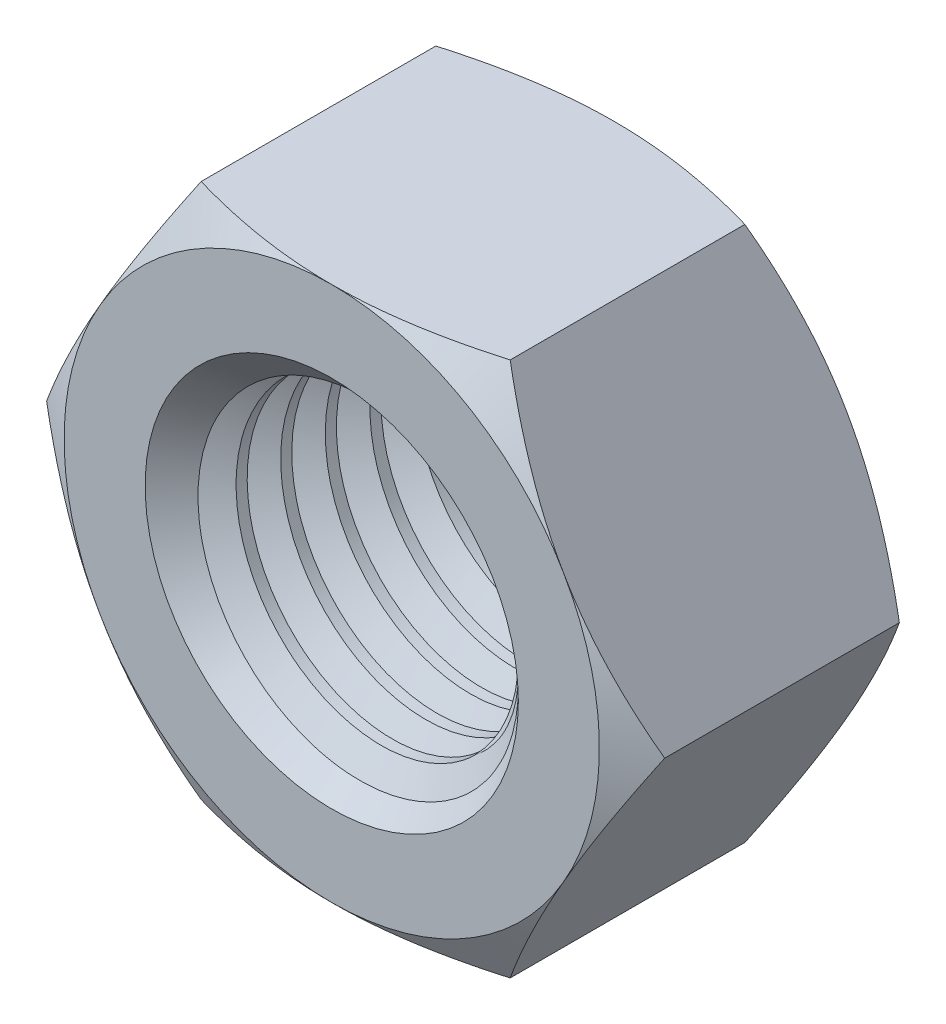
SolidWorks part; units mm, degrees
ref_plane "Front" through (0, 0, 0) normal (0, 0, 1) x (1, 0, 0)
ref_plane "Top" through (0, 0, 0) normal (0, 1, 0) x (1, 0, 0)
ref_plane "Right" through (0, 0, 0) normal (1, 0, 0) x (0, 0, -1)
sketch "Çizim1" plane through (0, 0, 0) normal (0, 0, 1) x (1, 0, 0)
  line L1 (20.7846, 0) -> (10.3923, 18)
  line L2 (10.3923, 18) -> (-10.3923, 18)
  line L3 (-10.3923, 18) -> (-20.7846, 0)
  line L4 (-20.7846, 0) -> (-10.3923, -18)
  line L5 (-10.3923, -18) -> (10.3923, -18)
  line L6 (10.3923, -18) -> (20.7846, 0)
  circle A0 centre (0, 0) radius 18 construction
  dimension "D1" = 36
extrude "Yükseklik-Ekstrüzyon1" add sketch "Çizim1" along normal blind 19
sketch "Çizim2" plane through (0, 0, 19) normal (0, 0, 1) x (1, 0, 0)
  circle A0 centre (0, 0) radius 18
extrude "Kes-Ekstrüzyon1" cut sketch "Çizim2" against normal blind 19 draft 60 flip side to cut
sketch "Çizim3" plane through (0, 0, 0) normal (0, 0, -1) x (-1, 0, 0)
  circle A0 centre (0, 0) radius 18
extrude "Kes-Ekstrüzyon2" cut sketch "Çizim3" against normal blind 19 draft 60 flip side to cut
sketch "Çizim4" plane through (0, 0, 19) normal (0, 0, 1) x (1, 0, 0)
  circle A0 centre (0, 0) radius 10.05
  dimension "D1" = 20.1
extrude "Kes-Ekstrüzyon3" cut sketch "Çizim4" against normal blind 19
chamfer "Pah1" distance 2.5 angle 45 2 edges at (10.05, 0, 0) (10.05, 0, 19)
sketch "Çizim5" plane through (0, 0, 0) normal (0, 0, -1) x (-1, 0, 0)
  circle A0 centre (0, 0) radius 10.05
  dimension "D1" = 20.1
curve "Helis/Spiral1" pitch 3 height 23 radius 10.05 centre (0, 0, 0) axis (0, 0, 1) start towards (1, 0, 0)
ref_plane "Düzlem1" through (-5.025, -8.7036, 23) normal (0.865, -0.4994, 0.0475) x (0.0411, -0.0237, -0.9989)
sketch "Çizim6" plane through (-5.025, -8.7036, 23) normal (0.865, -0.4994, 0.0475) x (0.0411, -0.0237, -0.9989)
  line L0 (-1.4852, 0.6225) -> (1.4852, 0.6225)
  line L1 (0, -1.95) -> (1.4852, 0.6225)
  line L3 (-1.4852, 0.6225) -> (0, -1.95)
  line L5 (0, 0.975) -> (-1.6887, 0.975) [skipped]
  circle A0 centre (0, 0) radius 0.975 construction
  dimension "D1" = 1.95
sweep "Kes-Süpür1" cut profiles "Çizim6" path "Helis/Spiral1" align with end faces yes
